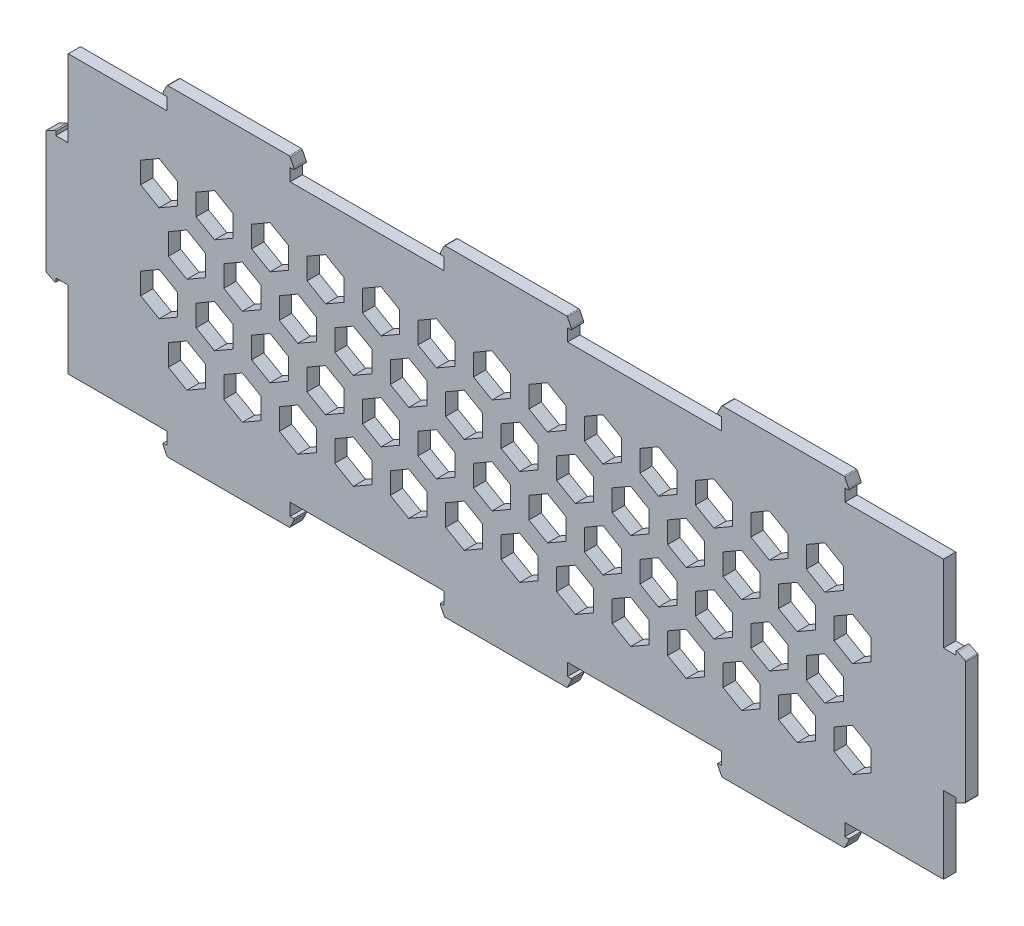
SolidWorks part; units mm, degrees
ref_plane "Front Plane" through (0, 0, 0) normal (0, 0, 1) x (1, 0, 0)
ref_plane "Top Plane" through (0, 0, 0) normal (0, 1, 0) x (1, 0, 0)
ref_plane "Right Plane" through (0, 0, 0) normal (1, 0, 0) x (0, 0, -1)
sketch "Sketch1" plane through (0, 0, 0) normal (0, 0, 1) x (1, 0, 0)
  line L0 (0, 0) -> (142, 0) construction
  line L1 (142, -22.5) -> (142, 22.5) construction
  line L2 (142, 22.5) -> (0, 22.5) construction
  line L3 (0, 22.5) -> (0, -22.5) construction
  line L8 (0, -22.5) -> (142, -22.5) construction
  line L30 (71, 22.5) -> (71, -22.5) construction
  line L31 (0, 10) -> (0, 22.5)
  line L32 (0, 22.5) -> (16, 22.5)
  line L35 (36, 22.5) -> (61, 22.5)
  line L37 (81, 22.5) -> (106, 22.5)
  line L39 (126, 22.5) -> (142, 22.5)
  line L40 (142, 22.5) -> (142, 10)
  line L42 (142, -10) -> (142, -22.5)
  line L43 (142, -22.5) -> (126, -22.5)
  line L46 (106, -22.5) -> (81, -22.5)
  line L48 (61, -22.5) -> (36, -22.5)
  line L50 (16, -22.5) -> (0, -22.5)
  line L51 (0, -22.5) -> (0, -10)
  line B0 (16, -22.5) -> (36, -22.5) construction
  line B1 (16.1618, -26.1) -> (35.8382, -26.1)
  line B2 (16, -22.5) -> (16, -24.5)
  line B3 (16, -26) -> (36, -26) construction
  line B4 (26, -26) -> (26, -22.5) construction
  line B5 (36, -22.5) -> (36, -24.5)
  line B6 (36.6, -24.8) -> (36, -26)
  line B7 (15.4, -24.8) -> (16, -26)
  line B8 (16, -24.5) -> (15.4, -24.5)
  line B9 (36, -24.5) -> (36.6, -24.5)
  arc B10 (16, -24.5) -> (15.4, -24.8) centre (15.7, -24.65) ccw construction
  arc B11 (16, -26) -> (16.1618, -26.1) centre (16.1618, -25.9191) ccw
  arc B12 (36, -26) -> (35.8382, -26.1) centre (35.8382, -25.9191) cw
  arc B13 (15.4, -24.5) -> (15.4, -24.8) centre (15.7, -24.65) ccw
  arc B14 (36.6, -24.5) -> (36.6, -24.8) centre (36.3, -24.65) cw
  line B15 (61, -22.5) -> (81, -22.5) construction
  line B16 (61.1618, -26.1) -> (80.8382, -26.1)
  line B17 (61, -22.5) -> (61, -24.5)
  line B18 (61, -26) -> (81, -26) construction
  line B19 (71, -26) -> (71, -22.5) construction
  line B20 (81, -22.5) -> (81, -24.5)
  line B21 (81.6, -24.8) -> (81, -26)
  line B22 (60.4, -24.8) -> (61, -26)
  line B23 (61, -24.5) -> (60.4, -24.5)
  line B24 (81, -24.5) -> (81.6, -24.5)
  arc B25 (61, -24.5) -> (60.4, -24.8) centre (60.7, -24.65) ccw construction
  arc B26 (61, -26) -> (61.1618, -26.1) centre (61.1618, -25.9191) ccw
  arc B27 (81, -26) -> (80.8382, -26.1) centre (80.8382, -25.9191) cw
  arc B28 (60.4, -24.5) -> (60.4, -24.8) centre (60.7, -24.65) ccw
  arc B29 (81.6, -24.5) -> (81.6, -24.8) centre (81.3, -24.65) cw
  line B30 (142, -10) -> (142, 10) construction
  line B31 (145.6, -9.8382) -> (145.6, 9.8382)
  line B32 (142, -10) -> (144, -10)
  line B33 (145.5, -10) -> (145.5, 10) construction
  line B34 (145.5, 0) -> (142, 0) construction
  line B35 (142, 10) -> (144, 10)
  line B36 (144.3, 10.6) -> (145.5, 10)
  line B37 (144.3, -10.6) -> (145.5, -10)
  line B38 (144, -10) -> (144, -10.6)
  line B39 (144, 10) -> (144, 10.6)
  arc B40 (144, -10) -> (144.3, -10.6) centre (144.15, -10.3) ccw construction
  arc B41 (145.5, -10) -> (145.6, -9.8382) centre (145.4191, -9.8382) ccw
  arc B42 (145.5, 10) -> (145.6, 9.8382) centre (145.4191, 9.8382) cw
  arc B43 (144, -10.6) -> (144.3, -10.6) centre (144.15, -10.3) ccw
  arc B44 (144, 10.6) -> (144.3, 10.6) centre (144.15, 10.3) cw
  line B45 (126, -22.5) -> (106, -22.5) construction
  line B46 (125.8382, -26.1) -> (106.1618, -26.1)
  line B47 (126, -22.5) -> (126, -24.5)
  line B48 (126, -26) -> (106, -26) construction
  line B49 (116, -26) -> (116, -22.5) construction
  line B50 (106, -22.5) -> (106, -24.5)
  line B51 (105.4, -24.8) -> (106, -26)
  line B52 (126.6, -24.8) -> (126, -26)
  line B53 (126, -24.5) -> (126.6, -24.5)
  line B54 (106, -24.5) -> (105.4, -24.5)
  arc B55 (126, -24.5) -> (126.6, -24.8) centre (126.3, -24.65) cw construction
  arc B56 (126, -26) -> (125.8382, -26.1) centre (125.8382, -25.9191) cw
  arc B57 (106, -26) -> (106.1618, -26.1) centre (106.1618, -25.9191) ccw
  arc B58 (126.6, -24.5) -> (126.6, -24.8) centre (126.3, -24.65) cw
  arc B59 (105.4, -24.5) -> (105.4, -24.8) centre (105.7, -24.65) ccw
  line B60 (16, 22.5) -> (36, 22.5) construction
  line B61 (16.1618, 26.1) -> (35.8382, 26.1)
  line B62 (16, 22.5) -> (16, 24.5)
  line B63 (16, 26) -> (36, 26) construction
  line B64 (26, 26) -> (26, 22.5) construction
  line B65 (36, 22.5) -> (36, 24.5)
  line B66 (36.6, 24.8) -> (36, 26)
  line B67 (15.4, 24.8) -> (16, 26)
  line B68 (16, 24.5) -> (15.4, 24.5)
  line B69 (36, 24.5) -> (36.6, 24.5)
  arc B70 (16, 24.5) -> (15.4, 24.8) centre (15.7, 24.65) cw construction
  arc B71 (16, 26) -> (16.1618, 26.1) centre (16.1618, 25.9191) cw
  arc B72 (36, 26) -> (35.8382, 26.1) centre (35.8382, 25.9191) ccw
  arc B73 (15.4, 24.5) -> (15.4, 24.8) centre (15.7, 24.65) cw
  arc B74 (36.6, 24.5) -> (36.6, 24.8) centre (36.3, 24.65) ccw
  line B75 (61, 22.5) -> (81, 22.5) construction
  line B76 (61.1618, 26.1) -> (80.8382, 26.1)
  line B77 (61, 22.5) -> (61, 24.5)
  line B78 (61, 26) -> (81, 26) construction
  line B79 (71, 26) -> (71, 22.5) construction
  line B80 (81, 22.5) -> (81, 24.5)
  line B81 (81.6, 24.8) -> (81, 26)
  line B82 (60.4, 24.8) -> (61, 26)
  line B83 (61, 24.5) -> (60.4, 24.5)
  line B84 (81, 24.5) -> (81.6, 24.5)
  arc B85 (61, 24.5) -> (60.4, 24.8) centre (60.7, 24.65) cw construction
  arc B86 (61, 26) -> (61.1618, 26.1) centre (61.1618, 25.9191) cw
  arc B87 (81, 26) -> (80.8382, 26.1) centre (80.8382, 25.9191) ccw
  arc B88 (60.4, 24.5) -> (60.4, 24.8) centre (60.7, 24.65) cw
  arc B89 (81.6, 24.5) -> (81.6, 24.8) centre (81.3, 24.65) ccw
  line B90 (126, 22.5) -> (106, 22.5) construction
  line B91 (125.8382, 26.1) -> (106.1618, 26.1)
  line B92 (126, 22.5) -> (126, 24.5)
  line B93 (126, 26) -> (106, 26) construction
  line B94 (116, 26) -> (116, 22.5) construction
  line B95 (106, 22.5) -> (106, 24.5)
  line B96 (105.4, 24.8) -> (106, 26)
  line B97 (126.6, 24.8) -> (126, 26)
  line B98 (126, 24.5) -> (126.6, 24.5)
  line B99 (106, 24.5) -> (105.4, 24.5)
  arc B100 (126, 24.5) -> (126.6, 24.8) centre (126.3, 24.65) ccw construction
  arc B101 (126, 26) -> (125.8382, 26.1) centre (125.8382, 25.9191) ccw
  arc B102 (106, 26) -> (106.1618, 26.1) centre (106.1618, 25.9191) cw
  arc B103 (126.6, 24.5) -> (126.6, 24.8) centre (126.3, 24.65) ccw
  arc B104 (105.4, 24.5) -> (105.4, 24.8) centre (105.7, 24.65) cw
  line B105 (0, -10) -> (0, 10) construction
  line B106 (-3.6, -9.8382) -> (-3.6, 9.8382)
  line B107 (0, -10) -> (-2, -10)
  line B108 (-3.5, -10) -> (-3.5, 10) construction
  line B109 (-3.5, 0) -> (0, 0) construction
  line B110 (0, 10) -> (-2, 10)
  line B111 (-2.3, 10.6) -> (-3.5, 10)
  line B112 (-2.3, -10.6) -> (-3.5, -10)
  line B113 (-2, -10) -> (-2, -10.6)
  line B114 (-2, 10) -> (-2, 10.6)
  arc B115 (-2, -10) -> (-2.3, -10.6) centre (-2.15, -10.3) cw construction
  arc B116 (-3.5, -10) -> (-3.6, -9.8382) centre (-3.4191, -9.8382) cw
  arc B117 (-3.5, 10) -> (-3.6, 9.8382) centre (-3.4191, 9.8382) ccw
  arc B118 (-2, -10.6) -> (-2.3, -10.6) centre (-2.15, -10.3) cw
  arc B119 (-2, 10.6) -> (-2.3, 10.6) centre (-2.15, 10.3) ccw
  dimension "D2" = 45
  dimension "D3" = 45
  dimension "D1" = 142
sketch_block_instance "insert_bloquant_20mm-2mm-1"
sketch_block "insert_bloquant_20mm-2mm" parameters "D1"=2, "D2"=1.5, "D3"=1.2, "D4"=20, "D5"=0.1, "D6"=0.6
sketch_block_instance "insert_bloquant_20mm-2mm-2"
sketch_block_instance "insert_bloquant_20mm-2mm-4"
sketch_block_instance "insert_bloquant_20mm-2mm-6"
sketch_block_instance "insert_bloquant_20mm-2mm-7"
sketch_block_instance "insert_bloquant_20mm-2mm-8"
sketch_block_instance "insert_bloquant_20mm-2mm-9"
sketch_block_instance "insert_bloquant_20mm-2mm-13"
extrude "Boss-Extrude1" add sketch "Sketch1" along normal blind 2 contours B114 B119 B111 B117 B106 B116 B112 B118 B113 B107 L51 L50 B2 B8 B13 B7 B11 B1 B12 B6 B14 B9 B5 L48 B17 B23 B28 B22 B26 B16 B27 B21 B29 B24 B20 L46 B50 B54 B59 B51 B57 B46 B56 B52 B58 B53 B47 L43 L42 B32 B38 region at (71, 0, 0)
sketch "Esquisse1" plane through (0, 0, 2) normal (0, 0, 1) x (1, 0, 0)
  line L0 (36, 22.5) -> (61, 22.5) construction
  line L1 (29.75, -5.6292) -> (31.25, 5.6292) construction
  line L2 (52.25, 5.6292) -> (53.75, -5.6292) construction
  line L3 (30.5, 0) -> (53, 0) construction
  line L4 (145.6, -9.8382) -> (145.6, 9.8382) construction
  line L5 (71, 26.1) -> (71, -26.1) construction
  line L6 (61.1618, 26.1) -> (80.8382, 26.1) construction
  line L7 (61.1618, -26.1) -> (80.8382, -26.1) construction
  line L8 (70.25, 5.6292) -> (71.75, -5.6292) construction
  point P10 (145.6, 0)
  point P18 (71, 0)
  line B0 (11.75, 9.9593) -> (14.75, 8.2272)
  line B1 (14.75, 8.2272) -> (17.75, 9.9593)
  line B2 (22.25, 5.6292) -> (19.25, 7.3612)
  line B3 (16.25, 5.6292) -> (16.25, 2.1651)
  line B4 (16.25, 2.1651) -> (19.25, 0.433)
  line B5 (19.25, 0.433) -> (22.25, 2.1651)
  line B6 (20.75, 13.4234) -> (20.75, 9.9593)
  line B7 (20.75, 9.9593) -> (23.75, 8.2272)
  line B8 (23.75, 8.2272) -> (26.75, 9.9593)
  line B9 (31.25, 5.6292) -> (28.25, 7.3612)
  line B10 (25.25, 5.6292) -> (25.25, 2.1651)
  line B11 (25.25, 2.1651) -> (28.25, 0.433)
  line B12 (28.25, 0.433) -> (31.25, 2.1651)
  line B13 (35.75, 13.4234) -> (32.75, 15.1554)
  line B14 (29.75, 13.4234) -> (29.75, 9.9593)
  line B15 (29.75, 9.9593) -> (32.75, 8.2272)
  line B16 (32.75, 8.2272) -> (35.75, 9.9593)
  line B17 (40.25, 5.6292) -> (37.25, 7.3612)
  line B18 (34.25, 5.6292) -> (34.25, 2.1651)
  line B19 (34.25, 2.1651) -> (37.25, 0.433)
  line B20 (37.25, 0.433) -> (40.25, 2.1651)
  line B21 (44.75, 13.4234) -> (41.75, 15.1554)
  line B22 (47.75, 13.4234) -> (47.75, 9.9593)
  line B23 (14.75, 15.1554) -> (11.75, 13.4234)
  line B24 (38.75, 13.4234) -> (38.75, 9.9593)
  line B25 (38.75, 9.9593) -> (41.75, 8.2272)
  line B26 (41.75, 8.2272) -> (44.75, 9.9593)
  line B27 (47.75, 9.9593) -> (50.75, 8.2272)
  line B28 (50.75, 8.2272) -> (53.75, 9.9593)
  line B29 (58.25, 5.6292) -> (55.25, 7.3612)
  line B30 (52.25, 5.6292) -> (52.25, 2.1651)
  line B31 (52.25, 2.1651) -> (55.25, 0.433)
  line B32 (55.25, 0.433) -> (58.25, 2.1651)
  line B33 (62.75, 13.4234) -> (59.75, 15.1554)
  line B34 (56.75, 13.4234) -> (56.75, 9.9593)
  line B35 (56.75, 9.9593) -> (59.75, 8.2272)
  line B36 (59.75, 8.2272) -> (62.75, 9.9593)
  line B37 (67.25, 5.6292) -> (64.25, 7.3612)
  line B38 (61.25, 5.6292) -> (61.25, 2.1651)
  line B39 (61.25, 2.1651) -> (64.25, 0.433)
  line B40 (64.25, 0.433) -> (67.25, 2.1651)
  line B41 (71.75, 13.4234) -> (68.75, 15.1554)
  line B42 (65.75, 13.4234) -> (65.75, 9.9593)
  line B43 (65.75, 9.9593) -> (68.75, 8.2272)
  line B44 (68.75, 8.2272) -> (71.75, 9.9593)
  line B45 (43.25, 2.1651) -> (46.25, 0.433)
  line B46 (46.25, 0.433) -> (49.25, 2.1651)
  line B47 (17.75, 13.4234) -> (14.75, 15.1554)
  line B48 (11.75, 13.4234) -> (11.75, 9.9593)
  line B49 (17.75, 9.9593) -> (17.75, 13.4234)
  line B50 (19.25, 7.3612) -> (16.25, 5.6292)
  line B51 (22.25, 2.1651) -> (22.25, 5.6292)
  line B52 (62.75, 9.9593) -> (62.75, 13.4234)
  line B53 (59.75, 15.1554) -> (56.75, 13.4234)
  line B54 (44.75, 9.9593) -> (44.75, 13.4234)
  line B55 (41.75, 15.1554) -> (38.75, 13.4234)
  line B56 (14.75, 11.6913) -> (71.75, 11.6913) construction
  line B57 (26.75, 9.9593) -> (26.75, 13.4234)
  line B58 (26.75, 13.4234) -> (23.75, 15.1554)
  line B59 (23.75, 15.1554) -> (20.75, 13.4234)
  line B60 (31.25, 2.1651) -> (31.25, 5.6292)
  line B61 (28.25, 7.3612) -> (25.25, 5.6292)
  line B62 (68.75, 15.1554) -> (65.75, 13.4234)
  line B63 (71.75, 9.9593) -> (71.75, 13.4234)
  line B64 (64.25, 7.3612) -> (61.25, 5.6292)
  line B65 (67.25, 2.1651) -> (67.25, 5.6292)
  line B66 (50.75, 15.1554) -> (47.75, 13.4234)
  line B67 (53.75, 13.4234) -> (50.75, 15.1554)
  line B68 (53.75, 9.9593) -> (53.75, 13.4234)
  line B69 (55.25, 7.3612) -> (52.25, 5.6292)
  line B70 (58.25, 2.1651) -> (58.25, 5.6292)
  line B71 (46.25, 7.3612) -> (43.25, 5.6292)
  line B72 (49.25, 5.6292) -> (46.25, 7.3612)
  line B73 (49.25, 2.1651) -> (49.25, 5.6292)
  line B74 (43.25, 5.6292) -> (43.25, 2.1651)
  line B75 (32.75, 15.1554) -> (29.75, 13.4234)
  line B76 (35.75, 9.9593) -> (35.75, 13.4234)
  line B77 (37.25, 7.3612) -> (34.25, 5.6292)
  line B78 (40.25, 2.1651) -> (40.25, 5.6292)
  line B79 (11.75, -5.6292) -> (14.75, -7.3612)
  line B80 (14.75, -7.3612) -> (17.75, -5.6292)
  line B81 (22.25, -9.9593) -> (19.25, -8.2272)
  line B82 (16.25, -9.9593) -> (16.25, -13.4234)
  line B83 (16.25, -13.4234) -> (19.25, -15.1554)
  line B84 (19.25, -15.1554) -> (22.25, -13.4234)
  line B85 (20.75, -2.1651) -> (20.75, -5.6292)
  line B86 (20.75, -5.6292) -> (23.75, -7.3612)
  line B87 (23.75, -7.3612) -> (26.75, -5.6292)
  line B88 (31.25, -9.9593) -> (28.25, -8.2272)
  line B89 (25.25, -9.9593) -> (25.25, -13.4234)
  line B90 (25.25, -13.4234) -> (28.25, -15.1554)
  line B91 (28.25, -15.1554) -> (31.25, -13.4234)
  line B92 (35.75, -2.1651) -> (32.75, -0.433)
  line B93 (29.75, -2.1651) -> (29.75, -5.6292)
  line B94 (29.75, -5.6292) -> (32.75, -7.3612)
  line B95 (32.75, -7.3612) -> (35.75, -5.6292)
  line B96 (40.25, -9.9593) -> (37.25, -8.2272)
  line B97 (34.25, -9.9593) -> (34.25, -13.4234)
  line B98 (34.25, -13.4234) -> (37.25, -15.1554)
  line B99 (37.25, -15.1554) -> (40.25, -13.4234)
  line B100 (44.75, -2.1651) -> (41.75, -0.433)
  line B101 (47.75, -2.1651) -> (47.75, -5.6292)
  line B102 (14.75, -0.433) -> (11.75, -2.1651)
  line B103 (38.75, -2.1651) -> (38.75, -5.6292)
  line B104 (38.75, -5.6292) -> (41.75, -7.3612)
  line B105 (41.75, -7.3612) -> (44.75, -5.6292)
  line B106 (47.75, -5.6292) -> (50.75, -7.3612)
  line B107 (50.75, -7.3612) -> (53.75, -5.6292)
  line B108 (58.25, -9.9593) -> (55.25, -8.2272)
  line B109 (52.25, -9.9593) -> (52.25, -13.4234)
  line B110 (52.25, -13.4234) -> (55.25, -15.1554)
  line B111 (55.25, -15.1554) -> (58.25, -13.4234)
  line B112 (62.75, -2.1651) -> (59.75, -0.433)
  line B113 (56.75, -2.1651) -> (56.75, -5.6292)
  line B114 (56.75, -5.6292) -> (59.75, -7.3612)
  line B115 (59.75, -7.3612) -> (62.75, -5.6292)
  line B116 (67.25, -9.9593) -> (64.25, -8.2272)
  line B117 (61.25, -9.9593) -> (61.25, -13.4234)
  line B118 (61.25, -13.4234) -> (64.25, -15.1554)
  line B119 (64.25, -15.1554) -> (67.25, -13.4234)
  line B120 (71.75, -2.1651) -> (68.75, -0.433)
  line B121 (65.75, -2.1651) -> (65.75, -5.6292)
  line B122 (65.75, -5.6292) -> (68.75, -7.3612)
  line B123 (68.75, -7.3612) -> (71.75, -5.6292)
  line B124 (43.25, -13.4234) -> (46.25, -15.1554)
  line B125 (46.25, -15.1554) -> (49.25, -13.4234)
  line B126 (17.75, -2.1651) -> (14.75, -0.433)
  line B127 (11.75, -2.1651) -> (11.75, -5.6292)
  line B128 (17.75, -5.6292) -> (17.75, -2.1651)
  line B129 (19.25, -8.2272) -> (16.25, -9.9593)
  line B130 (22.25, -13.4234) -> (22.25, -9.9593)
  line B131 (62.75, -5.6292) -> (62.75, -2.1651)
  line B132 (59.75, -0.433) -> (56.75, -2.1651)
  line B133 (44.75, -5.6292) -> (44.75, -2.1651)
  line B134 (41.75, -0.433) -> (38.75, -2.1651)
  line B135 (26.75, -5.6292) -> (26.75, -2.1651)
  line B136 (26.75, -2.1651) -> (23.75, -0.433)
  line B137 (23.75, -0.433) -> (20.75, -2.1651)
  line B138 (31.25, -13.4234) -> (31.25, -9.9593)
  line B139 (28.25, -8.2272) -> (25.25, -9.9593)
  line B140 (68.75, -0.433) -> (65.75, -2.1651)
  line B141 (71.75, -5.6292) -> (71.75, -2.1651)
  line B142 (64.25, -8.2272) -> (61.25, -9.9593)
  line B143 (67.25, -13.4234) -> (67.25, -9.9593)
  line B144 (50.75, -0.433) -> (47.75, -2.1651)
  line B145 (53.75, -2.1651) -> (50.75, -0.433)
  line B146 (53.75, -5.6292) -> (53.75, -2.1651)
  line B147 (55.25, -8.2272) -> (52.25, -9.9593)
  line B148 (58.25, -13.4234) -> (58.25, -9.9593)
  line B149 (46.25, -8.2272) -> (43.25, -9.9593)
  line B150 (49.25, -9.9593) -> (46.25, -8.2272)
  line B151 (49.25, -13.4234) -> (49.25, -9.9593)
  line B152 (43.25, -9.9593) -> (43.25, -13.4234)
  line B153 (32.75, -0.433) -> (29.75, -2.1651)
  line B154 (35.75, -5.6292) -> (35.75, -2.1651)
  line B155 (37.25, -8.2272) -> (34.25, -9.9593)
  line B156 (40.25, -13.4234) -> (40.25, -9.9593)
  line B157 (130.25, -9.9593) -> (127.25, -8.2272)
  line B158 (127.25, -8.2272) -> (124.25, -9.9593)
  line B159 (119.75, -5.6292) -> (122.75, -7.3612)
  line B160 (125.75, -5.6292) -> (125.75, -2.1651)
  line B161 (125.75, -2.1651) -> (122.75, -0.433)
  line B162 (122.75, -0.433) -> (119.75, -2.1651)
  line B163 (121.25, -13.4234) -> (121.25, -9.9593)
  line B164 (121.25, -9.9593) -> (118.25, -8.2272)
  line B165 (118.25, -8.2272) -> (115.25, -9.9593)
  line B166 (110.75, -5.6292) -> (113.75, -7.3612)
  line B167 (116.75, -5.6292) -> (116.75, -2.1651)
  line B168 (116.75, -2.1651) -> (113.75, -0.433)
  line B169 (113.75, -0.433) -> (110.75, -2.1651)
  line B170 (106.25, -13.4234) -> (109.25, -15.1554)
  line B171 (112.25, -13.4234) -> (112.25, -9.9593)
  line B172 (112.25, -9.9593) -> (109.25, -8.2272)
  line B173 (109.25, -8.2272) -> (106.25, -9.9593)
  line B174 (101.75, -5.6292) -> (104.75, -7.3612)
  line B175 (107.75, -5.6292) -> (107.75, -2.1651)
  line B176 (107.75, -2.1651) -> (104.75, -0.433)
  line B177 (104.75, -0.433) -> (101.75, -2.1651)
  line B178 (97.25, -13.4234) -> (100.25, -15.1554)
  line B179 (94.25, -13.4234) -> (94.25, -9.9593)
  line B180 (127.25, -15.1554) -> (130.25, -13.4234)
  line B181 (103.25, -13.4234) -> (103.25, -9.9593)
  line B182 (103.25, -9.9593) -> (100.25, -8.2272)
  line B183 (100.25, -8.2272) -> (97.25, -9.9593)
  line B184 (94.25, -9.9593) -> (91.25, -8.2272)
  line B185 (91.25, -8.2272) -> (88.25, -9.9593)
  line B186 (83.75, -5.6292) -> (86.75, -7.3612)
  line B187 (89.75, -5.6292) -> (89.75, -2.1651)
  line B188 (89.75, -2.1651) -> (86.75, -0.433)
  line B189 (86.75, -0.433) -> (83.75, -2.1651)
  line B190 (79.25, -13.4234) -> (82.25, -15.1554)
  line B191 (85.25, -13.4234) -> (85.25, -9.9593)
  line B192 (85.25, -9.9593) -> (82.25, -8.2272)
  line B193 (82.25, -8.2272) -> (79.25, -9.9593)
  line B194 (74.75, -5.6292) -> (77.75, -7.3612)
  line B195 (80.75, -5.6292) -> (80.75, -2.1651)
  line B196 (80.75, -2.1651) -> (77.75, -0.433)
  line B197 (77.75, -0.433) -> (74.75, -2.1651)
  line B198 (70.25, -13.4234) -> (73.25, -15.1554)
  line B199 (76.25, -13.4234) -> (76.25, -9.9593)
  line B200 (76.25, -9.9593) -> (73.25, -8.2272)
  line B201 (73.25, -8.2272) -> (70.25, -9.9593)
  line B202 (98.75, -2.1651) -> (95.75, -0.433)
  line B203 (95.75, -0.433) -> (92.75, -2.1651)
  line B204 (124.25, -13.4234) -> (127.25, -15.1554)
  line B205 (130.25, -13.4234) -> (130.25, -9.9593)
  line B206 (124.25, -9.9593) -> (124.25, -13.4234)
  line B207 (122.75, -7.3612) -> (125.75, -5.6292)
  line B208 (119.75, -2.1651) -> (119.75, -5.6292)
  line B209 (79.25, -9.9593) -> (79.25, -13.4234)
  line B210 (82.25, -15.1554) -> (85.25, -13.4234)
  line B211 (97.25, -9.9593) -> (97.25, -13.4234)
  line B212 (100.25, -15.1554) -> (103.25, -13.4234)
  line B213 (115.25, -9.9593) -> (115.25, -13.4234)
  line B214 (115.25, -13.4234) -> (118.25, -15.1554)
  line B215 (118.25, -15.1554) -> (121.25, -13.4234)
  line B216 (110.75, -2.1651) -> (110.75, -5.6292)
  line B217 (113.75, -7.3612) -> (116.75, -5.6292)
  line B218 (73.25, -15.1554) -> (76.25, -13.4234)
  line B219 (70.25, -9.9593) -> (70.25, -13.4234)
  line B220 (77.75, -7.3612) -> (80.75, -5.6292)
  line B221 (74.75, -2.1651) -> (74.75, -5.6292)
  line B222 (91.25, -15.1554) -> (94.25, -13.4234)
  line B223 (88.25, -13.4234) -> (91.25, -15.1554)
  line B224 (88.25, -9.9593) -> (88.25, -13.4234)
  line B225 (86.75, -7.3612) -> (89.75, -5.6292)
  line B226 (83.75, -2.1651) -> (83.75, -5.6292)
  line B227 (95.75, -7.3612) -> (98.75, -5.6292)
  line B228 (92.75, -5.6292) -> (95.75, -7.3612)
  line B229 (92.75, -2.1651) -> (92.75, -5.6292)
  line B230 (98.75, -5.6292) -> (98.75, -2.1651)
  line B231 (109.25, -15.1554) -> (112.25, -13.4234)
  line B232 (106.25, -9.9593) -> (106.25, -13.4234)
  line B233 (104.75, -7.3612) -> (107.75, -5.6292)
  line B234 (101.75, -2.1651) -> (101.75, -5.6292)
  line B235 (130.25, 5.6292) -> (127.25, 7.3612)
  line B236 (127.25, 7.3612) -> (124.25, 5.6292)
  line B237 (119.75, 9.9593) -> (122.75, 8.2272)
  line B238 (125.75, 9.9593) -> (125.75, 13.4234)
  line B239 (125.75, 13.4234) -> (122.75, 15.1554)
  line B240 (122.75, 15.1554) -> (119.75, 13.4234)
  line B241 (121.25, 2.1651) -> (121.25, 5.6292)
  line B242 (121.25, 5.6292) -> (118.25, 7.3612)
  line B243 (118.25, 7.3612) -> (115.25, 5.6292)
  line B244 (110.75, 9.9593) -> (113.75, 8.2272)
  line B245 (116.75, 9.9593) -> (116.75, 13.4234)
  line B246 (116.75, 13.4234) -> (113.75, 15.1554)
  line B247 (113.75, 15.1554) -> (110.75, 13.4234)
  line B248 (106.25, 2.1651) -> (109.25, 0.433)
  line B249 (112.25, 2.1651) -> (112.25, 5.6292)
  line B250 (112.25, 5.6292) -> (109.25, 7.3612)
  line B251 (109.25, 7.3612) -> (106.25, 5.6292)
  line B252 (101.75, 9.9593) -> (104.75, 8.2272)
  line B253 (107.75, 9.9593) -> (107.75, 13.4234)
  line B254 (107.75, 13.4234) -> (104.75, 15.1554)
  line B255 (104.75, 15.1554) -> (101.75, 13.4234)
  line B256 (97.25, 2.1651) -> (100.25, 0.433)
  line B257 (94.25, 2.1651) -> (94.25, 5.6292)
  line B258 (127.25, 0.433) -> (130.25, 2.1651)
  line B259 (103.25, 2.1651) -> (103.25, 5.6292)
  line B260 (103.25, 5.6292) -> (100.25, 7.3612)
  line B261 (100.25, 7.3612) -> (97.25, 5.6292)
  line B262 (94.25, 5.6292) -> (91.25, 7.3612)
  line B263 (91.25, 7.3612) -> (88.25, 5.6292)
  line B264 (83.75, 9.9593) -> (86.75, 8.2272)
  line B265 (89.75, 9.9593) -> (89.75, 13.4234)
  line B266 (89.75, 13.4234) -> (86.75, 15.1554)
  line B267 (86.75, 15.1554) -> (83.75, 13.4234)
  line B268 (79.25, 2.1651) -> (82.25, 0.433)
  line B269 (85.25, 2.1651) -> (85.25, 5.6292)
  line B270 (85.25, 5.6292) -> (82.25, 7.3612)
  line B271 (82.25, 7.3612) -> (79.25, 5.6292)
  line B272 (74.75, 9.9593) -> (77.75, 8.2272)
  line B273 (80.75, 9.9593) -> (80.75, 13.4234)
  line B274 (80.75, 13.4234) -> (77.75, 15.1554)
  line B275 (77.75, 15.1554) -> (74.75, 13.4234)
  line B276 (70.25, 2.1651) -> (73.25, 0.433)
  line B277 (76.25, 2.1651) -> (76.25, 5.6292)
  line B278 (76.25, 5.6292) -> (73.25, 7.3612)
  line B279 (73.25, 7.3612) -> (70.25, 5.6292)
  line B280 (98.75, 13.4234) -> (95.75, 15.1554)
  line B281 (95.75, 15.1554) -> (92.75, 13.4234)
  line B282 (124.25, 2.1651) -> (127.25, 0.433)
  line B283 (130.25, 2.1651) -> (130.25, 5.6292)
  line B284 (124.25, 5.6292) -> (124.25, 2.1651)
  line B285 (122.75, 8.2272) -> (125.75, 9.9593)
  line B286 (119.75, 13.4234) -> (119.75, 9.9593)
  line B287 (79.25, 5.6292) -> (79.25, 2.1651)
  line B288 (82.25, 0.433) -> (85.25, 2.1651)
  line B289 (97.25, 5.6292) -> (97.25, 2.1651)
  line B290 (100.25, 0.433) -> (103.25, 2.1651)
  line B291 (115.25, 5.6292) -> (115.25, 2.1651)
  line B292 (115.25, 2.1651) -> (118.25, 0.433)
  line B293 (118.25, 0.433) -> (121.25, 2.1651)
  line B294 (110.75, 13.4234) -> (110.75, 9.9593)
  line B295 (113.75, 8.2272) -> (116.75, 9.9593)
  line B296 (73.25, 0.433) -> (76.25, 2.1651)
  line B297 (70.25, 5.6292) -> (70.25, 2.1651)
  line B298 (77.75, 8.2272) -> (80.75, 9.9593)
  line B299 (74.75, 13.4234) -> (74.75, 9.9593)
  line B300 (91.25, 0.433) -> (94.25, 2.1651)
  line B301 (88.25, 2.1651) -> (91.25, 0.433)
  line B302 (88.25, 5.6292) -> (88.25, 2.1651)
  line B303 (86.75, 8.2272) -> (89.75, 9.9593)
  line B304 (83.75, 13.4234) -> (83.75, 9.9593)
  line B305 (95.75, 8.2272) -> (98.75, 9.9593)
  line B306 (92.75, 9.9593) -> (95.75, 8.2272)
  line B307 (92.75, 13.4234) -> (92.75, 9.9593)
  line B308 (98.75, 9.9593) -> (98.75, 13.4234)
  line B309 (109.25, 0.433) -> (112.25, 2.1651)
  line B310 (106.25, 5.6292) -> (106.25, 2.1651)
  line B311 (104.75, 8.2272) -> (107.75, 9.9593)
  line B312 (101.75, 13.4234) -> (101.75, 9.9593)
sketch_block_instance "Alveole_9mm_3mm_8x2-1"
sketch_block "Alveole_9mm_3mm_8x2" parameters "D1"=7, "D2"=1.5, "D3"=13.2857, "D4"=14
sketch_block_instance "Alveole_9mm_3mm_8x2-3"
sketch_block_instance "Alveole_9mm_3mm_8x2-4"
sketch_block_instance "Alveole_9mm_3mm_8x2-5"
extrude "Enlèv. mat.-Extru.1" cut sketch "Esquisse1" against normal through all
